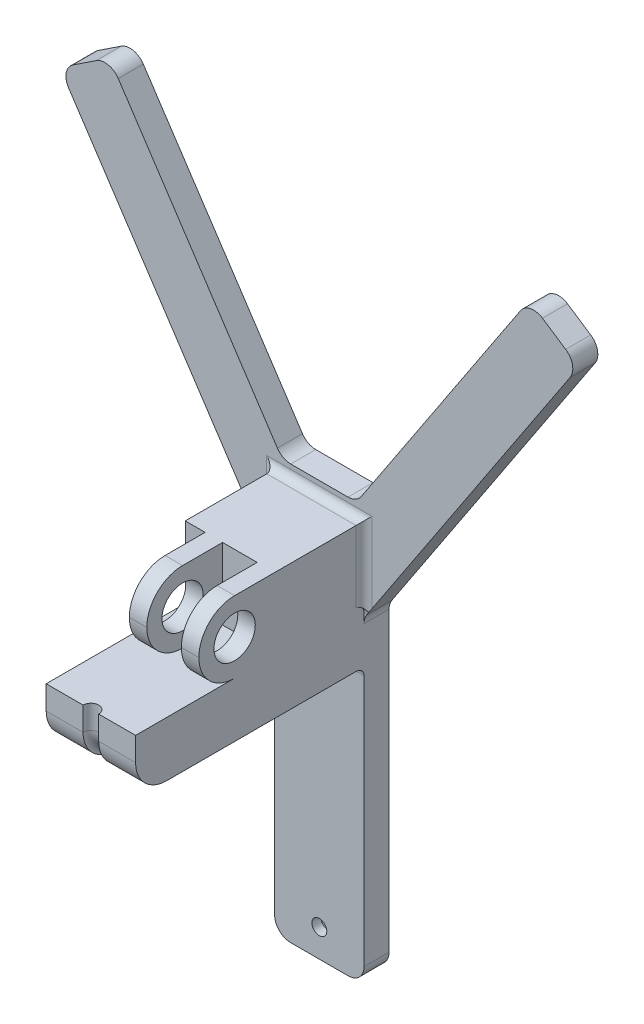
SolidWorks part; units mm, degrees
ref_plane "Plan de face" through (0, 0, 0) normal (0, 0, 1) x (1, 0, 0)
ref_plane "Plan de dessus" through (0, 0, 0) normal (0, 1, 0) x (1, 0, 0)
ref_plane "Plan de droite" through (0, 0, 0) normal (1, 0, 0) x (0, 0, -1)
sketch "Sketch1" plane through (0, 0, 0) normal (0, 0, 1) x (1, 0, 0)
  line L18 (-11.895, 65.5892) -> (11.895, 65.5892)
  line L19 (11.895, 65.5892) -> (67.0848, 148.9804)
  line L20 (67.0848, 148.9804) -> (82.9708, 138.4667)
  line L21 (82.9708, 138.4667) -> (14.2875, 34.687)
  line L23 (14.2875, 34.687) -> (14.2875, -66.913)
  line L24 (14.2875, -66.913) -> (-14.2875, -66.913)
  line L25 (-14.2875, -66.913) -> (-14.2875, 34.687)
  line L26 (-14.2875, 34.687) -> (-82.9708, 138.4667)
  line L27 (-82.9708, 138.4667) -> (-67.0848, 148.9804)
  line L28 (-67.0848, 148.9804) -> (-11.895, 65.5892)
  line L29 (-14.2875, 34.687) -> (14.2875, 34.687) construction
  point P2 (0, 34.687)
  point P12 (0, 65.5892)
  dimension "D1" = 28.575
  dimension "D2" = 19.05
  dimension "D3" = 100
  dimension "D4" = 100
  dimension "D5" = 101.6
extrude "Boss-Extrude1" add sketch "Sketch1" along normal blind 8
sketch "Sketch3" plane through (0, 0, 8) normal (0, 0, 1) x (1, 0, 0)
  line L0 (0, 65.5892) -> (0, 34.687) construction
  line L5 (14.2875, 38.7081) -> (-14.2875, 38.7081)
  line L6 (14.2875, 38.7081) -> (14.2875, 61.5681)
  line L7 (14.2875, 61.5681) -> (-14.2875, 61.5681)
  line L8 (-14.2875, 38.7081) -> (-14.2875, 61.5681)
  line L9 (14.2875, 38.7081) -> (-14.2875, 61.5681) construction
  line L10 (14.2875, 61.5681) -> (-14.2875, 38.7081) construction
  line L12 (11.895, 65.5892) -> (-11.895, 65.5892) construction
  point P0 (0, 50.1381)
  point P15 (0, 50.1381)
  dimension "D1" = 28.575
  dimension "D2" = 22.86
extrude "Boss-Extrude2" add sketch "Sketch3" along normal blind 52.8
sketch "Sketch6" plane through (0, 0, 8) normal (0, 0, 1) x (1, 0, 0)
  line L6 (-14.2875, 34.687) -> (-14.2875, -66.913) construction
  line L11 (-14.2875, 38.7081) -> (14.2875, 38.7081)
  line L12 (-14.2875, 38.7081) -> (-14.2875, -66.913)
  line L13 (-14.2875, -66.913) -> (14.2875, -66.913)
  line L14 (14.2875, 38.7081) -> (14.2875, -66.913)
  line L15 (-14.2875, -66.913) -> (14.2875, -66.913) construction
  line L16 (14.2875, -66.913) -> (14.2875, 34.687) construction
  line L17 (-14.2875, 38.7081) -> (14.2875, 38.7081) construction
extrude "Boss-Extrude3" [suppressed] add sketch "Sketch6" along normal blind 5.08
fillet "Fillet1" radius 5.08 10 edges at (-14.2875, -66.913, 4) (14.2875, -66.913, 4) (82.9708, 138.4667, 4) (67.0848, 148.9804, 4) (-67.0848, 148.9804, 4) (-82.9708, 138.4667, 4) (-11.895, 65.5892, 4) (11.895, 65.5892, 4) (14.2875, 34.687, 4) (-14.2875, 34.687, 4)
sketch "Sketch4" plane through (0, 38.7081, 0) normal (0, -1, 0) x (1, 0, 0)
  line L0 (-14.2875, 60.8) -> (14.2875, 60.8) construction
  line L1 (-14.2875, 60.8) -> (-7.9375, 60.8)
  line L2 (-14.2875, 60.8) -> (-14.2875, 36.575)
  line L3 (-14.2875, 36.575) -> (-7.9375, 36.575)
  line L4 (-7.9375, 60.8) -> (-7.9375, 36.575)
  line L5 (-2.3495, 60.8) -> (8.6995, 60.8)
  line L6 (-2.3495, 60.8) -> (-2.3495, 36.575)
  line L7 (-2.3495, 36.575) -> (8.6995, 36.575)
  line L8 (8.6995, 60.8) -> (8.6995, 36.575)
  line L9 (14.2875, 60.8) -> (14.2875, 8) construction
  dimension "D1" = 5.588
  dimension "D2" = 5.588
  dimension "D3" = 24.225
  dimension "D4" = 24.225
  dimension "D5" = 6.35
extrude "Cut-Extrude1" cut sketch "Sketch4" against normal through all
fillet "Fillet3" radius 11.43 4 edges at (11.4935, 61.5681, 60.8) (-5.1435, 61.5681, 60.8) (11.4935, 38.7081, 60.8) (-5.1435, 38.7081, 60.8)
sketch "Sketch5" plane through (-7.9375, 0, 0) normal (-1, 0, 0) x (0, 0, 1)
  circle A0 centre (49.37, 50.1381) radius 6.604
  dimension "D1" = 13.208
extrude "Cut-Extrude2" cut sketch "Sketch5" against normal through all
fillet "Fillet6" [suppressed] radius 2.54
sketch "Sketch7" plane through (0, 0, 0) normal (0, 0, -1) x (-1, 0, 0)
  line L0 (9.2075, -66.913) -> (-9.2075, -66.913) construction
  line L1 (14.2875, 33.1582) -> (14.2875, -61.833) construction
  circle A0 centre (0, -58.023) radius 4.2333
  dimension "D1" = 8.4667
  dimension "D2" = 8.89
  dimension "D3" = 14.2875
extrude "Cut-Extrude3" cut sketch "Sketch7" against normal blind 5.08
sketch "Sketch8" plane through (0, 0, 5.08) normal (0, 0, -1) x (-1, 0, 0)
  line L0 (14.2875, 33.1582) -> (14.2875, -61.833) construction
  line L2 (9.2075, -66.913) -> (-9.2075, -66.913) construction
  circle A0 centre (0, -58.023) radius 2.3812
  dimension "D1" = 4.7625
  dimension "D2" = 14.2875
  dimension "D3" = 8.89
extrude "Cut-Extrude4" cut sketch "Sketch8" against normal through all
fillet "Fillet7" radius 2.54 4 edges at (-14.2875, 50.1381, 8) (0, 61.5681, 8) (14.2875, 50.1381, 8) (0, 38.7081, 8)
sketch "Sketch9" plane through (-14.2875, 0, 0) normal (-1, 0, 0) x (0, 0, 1)
  line L6 (10.54, 38.7081) -> (36.575, 38.7081)
  line L26 (36.575, 38.7081) -> (81.0276, 38.7081)
  line L27 (8, 36.1681) -> (8, 21.1681)
  line L28 (8, 33.1582) -> (8, -61.833) construction
  line L29 (8, 21.1681) -> (81.0276, 21.1681)
  line L30 (81.0276, 21.1681) -> (81.0276, 38.7081)
  arc A0 (10.54, 38.7081) -> (8.1798, 37.1067) centre (10.54, 36.1681) ccw
  arc A1 (10.54, 38.7081) -> (8.1798, 37.1067) centre (10.54, 36.1681) ccw construction
  arc A2 (8.1798, 37.1067) -> (8, 36.1681) centre (10.54, 36.1681) ccw
  arc A3 (8.1798, 37.1067) -> (8, 36.1681) centre (10.54, 36.1681) ccw construction
  dimension "D1" = 15
extrude "Boss-Extrude4" add sketch "Sketch9" against normal up to surface (28.575 mm away) up to face at (14.2875, -14.3374, 4)
ref_plane "Plan1" through (0, 0, 0) normal (-1, 0, 0) x (0, 0, 1)
fillet "Fillet8" radius 10 1 edges at (0, 21.1681, 81.0276)
sketch "Sketch13" plane through (0, 0, 0) normal (-1, 0, 0) x (0, 0, 1)
  line L0 (81.0276, 38.7081) -> (81.0276, 31.1681)
  line L1 (71.0276, 21.1681) -> (56.0276, 21.1681)
  line L3 (8, 21.1681) -> (71.0276, 21.1681) construction
  arc A0 (81.0276, 31.1681) -> (71.0276, 21.1681) centre (71.0276, 31.1681) cw
  dimension "D1" = 15
sweep "Cut-Sweep1" cut path "Sketch13" circular profile diameter 5 parameters "D3"=5
fillet "Fillet9" radius 2.54 1 edges at (0, 21.1681, 8)
